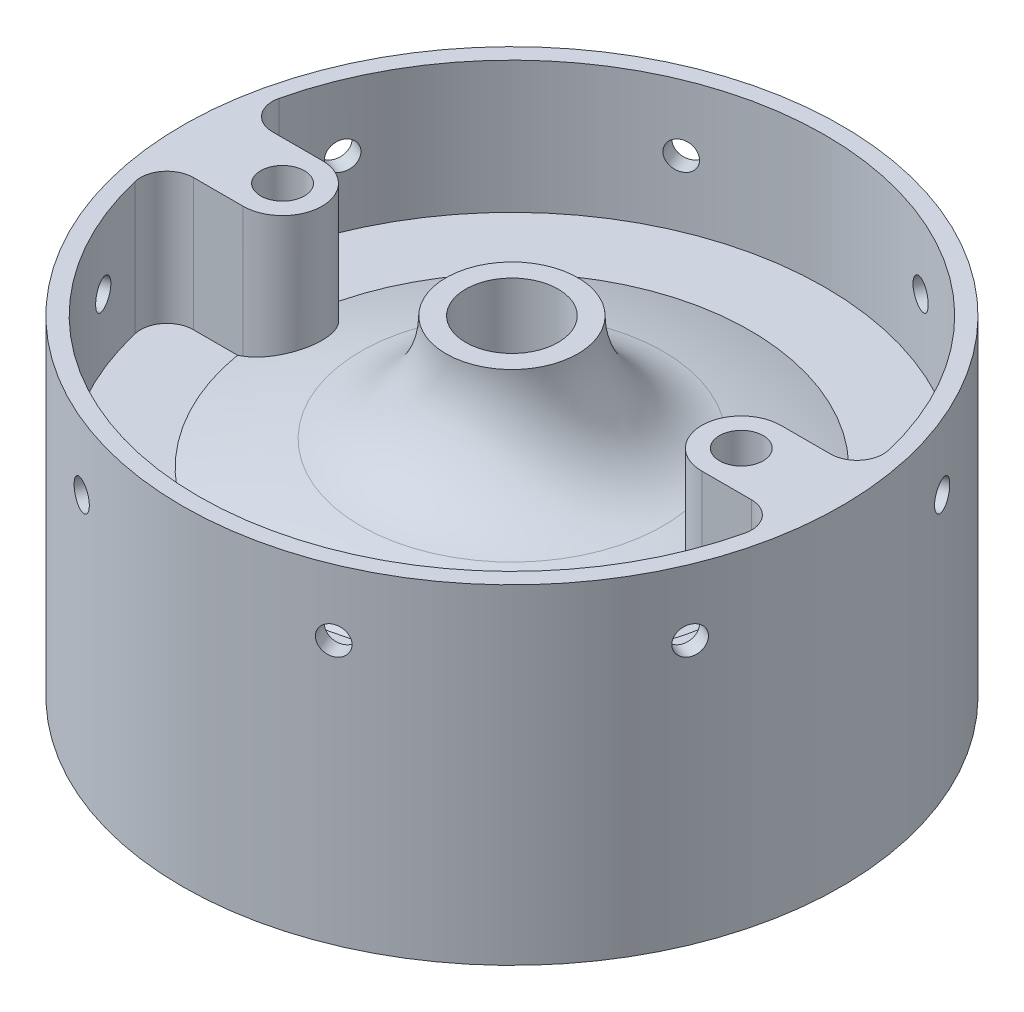
SolidWorks part; units mm, degrees
material "6061-T6 (SS)"
ref_plane "Front Plane" through (0, 0, 0) normal (0, 0, 1) x (1, 0, 0)
ref_plane "Top Plane" through (0, 0, 0) normal (0, 1, 0) x (1, 0, 0)
ref_plane "Right Plane" through (0, 0, 0) normal (1, 0, 0) x (0, 0, -1)
ref_axis "Axis1" through (0, 127.061, 0) along (0, -1, 0)
sketch "Sketch1" plane through (0, 0, 0) normal (0, 0, 1) x (1, 0, 0)
  line L0 (-63.5, 0) -> (-63.5, 63.5)
  line L1 (-60.325, 0) -> (-63.5, 0)
  line L2 (0, 127.061) -> (0, -81.9141) construction
  line L3 (-8.9065, 63.5) -> (-12.7, 63.5)
  line L4 (55, 0) -> (-55, 0) construction
  line L7 (-60.325, 63.5) -> (-63.5, 63.5)
  line L8 (-63.5, 0) -> (-60.325, 0)
  line L9 (-60.325, 38.1) -> (-45.888, 38.1)
  line L10 (-8.9065, 63.5) -> (-8.9065, 48.26)
  line L11 (-60.325, 38.1) -> (-60.325, 63.5)
  line L16 (-60.325, 0) -> (-58.0548, 12.875)
  arc A0 (-58.0548, 12.875) -> (-45.888, 30.638) centre (-39.0048, 12.875) cw
  arc A1 (-45.888, 30.638) -> (-19.4461, 37.7204) centre (0, -87.782) cw
  arc A2 (-29.1382, 42.9963) -> (-12.7, 63.5) centre (-33.7065, 63.5) ccw
  arc A3 (-45.888, 38.1) -> (-29.1382, 42.9963) centre (0, -87.782) cw
  arc A4 (-8.9065, 48.26) -> (-19.4461, 37.7204) centre (-19.4461, 48.26) cw
  point P8 (-60.5743, 0)
  dimension "D5" = 19.05
  dimension "D6" = 127
  dimension "D7" = 133.985
  dimension "D8" = 63.5
  dimension "D14" = 15.24
  dimension "D2" = 260
  dimension "D9" = 25.4
  dimension "D10" = 3.175
  dimension "D11" = 12.7
  dimension "D13" = 8.9065
  dimension "D15" = 3.175
  dimension "D16" = 63.5
revolve "Revolve2" add sketch "Sketch1" angle 360 about axis through (0, 127.061, 0) along (0, -1, 0) region at (-41.9326, 36.3496, 0)
sketch "Sketch2" plane through (0, 0, 0) normal (0, 0, 1) x (1, 0, 0)
  line L0 (0, 127.061) -> (0, -81.9141) construction
  line L1 (0, 87.1374) -> (-97.8719, 87.1374)
  line L2 (0, 87.1374) -> (0, -26.2798)
  line L3 (0, -26.2798) -> (-97.8719, -26.2798)
  line L4 (-97.8719, 87.1374) -> (-97.8719, -26.2798)
revolve "Cut-Revolve1" [suppressed] cut sketch "Sketch2" angle 315 about axis through (0, 127.061, 0) along (0, -1, 0)
ref_plane "Plane1" through (0, 50.8, 0) normal (0, 1, 0) x (1, 0, 0)
ref_plane "Plane2" through (0, 0, 0) normal (0.9239, 0, 0.3827) x (0, -1, 0)
ref_axis "Axis2" through (83.9699, 50.8, -202.7212) along (-0.3827, 0, 0.9239)
hole_wizard "#3 (0.213) Diameter Hole1" positions "3DSketch3" profile "Sketch5" hole size "#3" standard "ANSI Inch"
sketch3d "3DSketch3"
  line L0 (83.9699, 50.8, -202.7212) -> (-38.5912, 50.8, 93.1674) construction
  point P0 (-24.3004, 50.8, 58.6664)
sketch "Sketch5" plane through (-24.3004, 50.8, 58.6664) normal (0, 1, 0) x (0.9239, 0, 0.3827)
  line L0 (0, 0) -> (0, 13.3094)
  line L1 (0, 13.3094) -> (2.7051, 11.684)
  line L2 (2.7051, 11.684) -> (2.7051, 0)
  line L5 (2.7051, 0) -> (0, 0)
  line L10 (0, 13.3094) -> (-2.7051, 11.684) construction
  line L11 (0, -6.35) -> (0, 107.95) construction
  dimension "Hole Dia." = 5.4102
  dimension "Hole Depth" = 11.684
  dimension "Drill Angle" = 118
pattern_circular "CirPattern1" count 8 over 360 about axis through (0, 127.061, 0) along (0, -1, 0) of "#3 (0.213) Diameter Hole1"
cosmetic thread "Cosmetic Thread1" parameters "D2"=6.35
hole_wizard "Q (0.332) Diameter Hole2" positions "Sketch9" profile "Sketch10" hole size "Q" standard "ANSI Inch" end condition through all
sketch "Sketch9" plane through (0, 38.1, 0) normal (0, 1, 0) x (1, 0, 0)
  line L0 (-55, 0) -> (55, 0) construction
  circle A1 centre (0, 0) radius 45.888 construction
  point P0 (-44.196, 0)
  dimension "D1" = 44.196
sketch "Sketch10" plane through (-44.196, 38.1, 0) normal (1, 0, 0) x (0, 0, 1)
  line L0 (0, 0) -> (0, 38.1)
  line L1 (0, 38.1) -> (4.2164, 38.1)
  line L2 (4.2164, 38.1) -> (4.2164, 0)
  line L5 (4.2164, 0) -> (0, 0)
  line L11 (0, -6.35) -> (0, 107.95) construction
  dimension "Thru Hole Dia." = 8.4328
  dimension "Thru Hole Depth" = 38.1
sketch "Sketch11" plane through (0, 38.1, 0) normal (0, 1, 0) x (1, 0, 0)
  line L0 (-59.8418, 7.62) -> (-44.196, 7.62)
  line L1 (-59.8418, -7.6199) -> (-44.1961, -7.62)
  circle A0 centre (0, 0) radius 60.325 construction
  arc A2 (-44.196, 7.62) -> (-44.1961, -7.62) centre (-44.196, 0) cw
  circle A3 centre (-44.196, 0) radius 4.2164 construction
  circle A5 centre (0, 0) radius 60.325
  arc A6 (-59.8418, 7.62) -> (-59.8418, -7.6199) centre (0, 0) ccw
  dimension "D1" = 7.62
  dimension "D2" = 7.62
  dimension "D3" = 180
  dimension "D4" = 0
extrude "Boss-Extrude1" add sketch "Sketch11" along normal up to surface (25.4 mm away) up to face at (0, 63.5, 63.5)
fillet "Fillet1" radius 5.08 2 edges at (-59.8418, 50.8, -7.62) (-59.8418, 50.8, 7.6199)
hole_wizard "Q (0.332) Diameter Hole3" positions "Sketch12" profile "Sketch13" hole size "Q" standard "ANSI Inch" end condition up to next
sketch "Sketch12" plane through (0, 38.1, 0) normal (0, -1, 0) x (-1, 0, 0)
  circle A0 centre (44.196, 0) radius 4.2164 construction
  point P0 (44.196, 0)
sketch "Sketch13" plane through (-44.196, 38.1, 0) normal (1, 0, 0) x (0, 0, -1)
  line L0 (0, 0) -> (0, 25.401)
  line L1 (0, 25.401) -> (4.2164, 25.401)
  line L2 (4.2164, 25.401) -> (4.2164, 0)
  line L5 (4.2164, 0) -> (0, 0)
  line L11 (0, -6.35) -> (0, 107.95) construction
  dimension "Thru Hole Dia." = 8.4328
  dimension "Thru Hole Depth" = 25.401
mirror "Mirror1" about plane through (0, 0, 0) normal (1, 0, 0) of "Boss-Extrude1", "Fillet1", "Q (0.332) Diameter Hole3"
